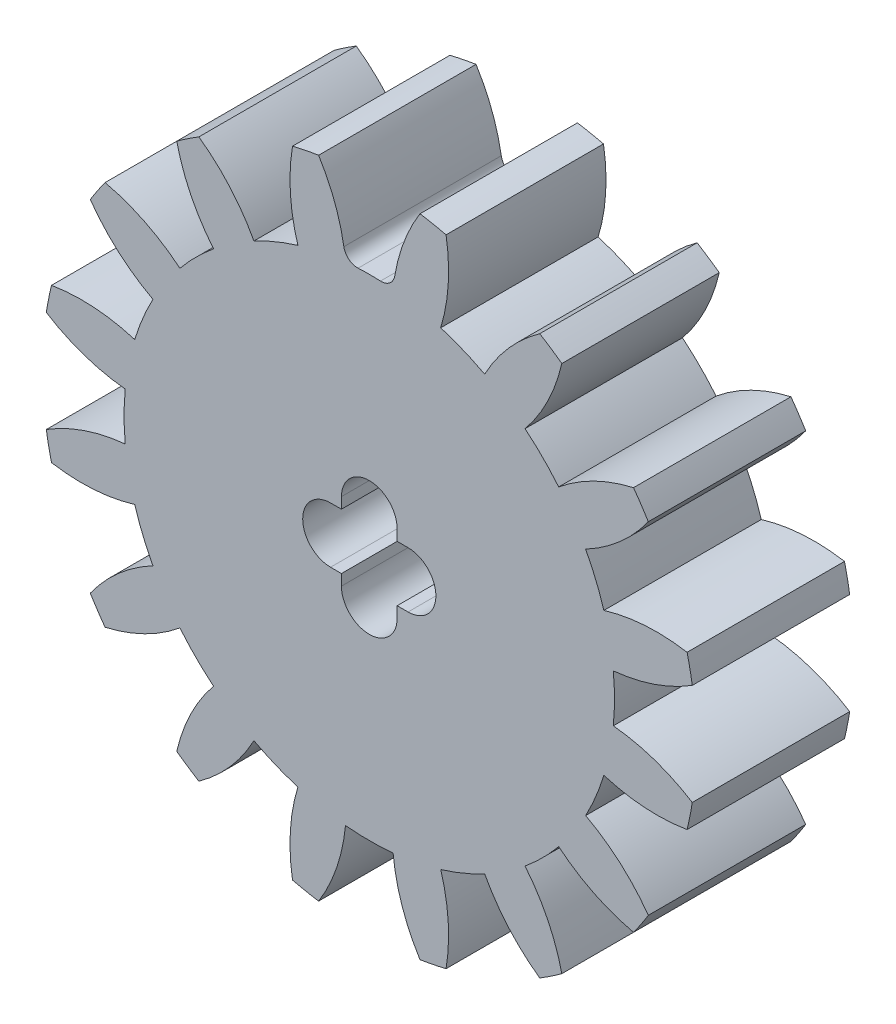
SolidWorks part; units mm, degrees
ref_plane "Front Plane" through (0, 0, 0) normal (0, 0, 1) x (1, 0, 0)
ref_plane "Top Plane" through (0, 0, 0) normal (0, 1, 0) x (1, 0, 0)
ref_plane "Right Plane" through (0, 0, 0) normal (1, 0, 0) x (0, 0, -1)
sketch "Sketch1" plane through (0, 0, 0) normal (0, 0, 1) x (1, 0, 0)
  line L0 (0, -1.6) -> (0, 1.6) construction
  line L1 (-1.15, -1.6) -> (-1.15, 1.6)
  line L2 (1.15, -1.6) -> (1.15, 1.6)
  line L3 (-1.6, 0) -> (1.6, 0) construction
  line L4 (-1.6, 1.15) -> (1.6, 1.15)
  line L5 (-1.6, -1.15) -> (1.6, -1.15)
  circle A0 centre (0, 0) radius 13.5
  arc A2 (-1.15, -1.6) -> (1.15, -1.6) centre (0, -1.6) ccw
  arc A3 (1.15, 1.6) -> (-1.15, 1.6) centre (0, 1.6) ccw
  arc A4 (-1.6, 1.15) -> (-1.6, -1.15) centre (-1.6, 0) ccw
  arc A5 (1.6, -1.15) -> (1.6, 1.15) centre (1.6, 0) ccw
  point P5 (0, 0)
  point P11 (0, 0)
  dimension "D2" = 27
  dimension "D1" = 5.5
  dimension "D3" = 5.5
  dimension "D4" = 2.3
  dimension "D5" = 2.3
extrude "Boss-Extrude1" add sketch "Sketch1" along normal mid plane 6.5 contours A0 A5 L5 L2 A2 L1 A4 L4 A3 region at (-13.1182, 0, 0)
sketch "Sketch2" plane through (0, 0, 0) normal (0, 0, 1) x (1, 0, 0)
  line L0 (0, 0) -> (0, 13.5) construction
  line L1 (0, 0) -> (-0.9822, 10.0772) construction
  line L2 (0, 8.0719) -> (-4.2467, 19.7397) construction
  arc A0 (1.3999, 11.9181) -> (-1.3999, 11.9181) centre (0, 0) ccw construction
  arc A1 (0.9822, 10.0772) -> (-0.9822, 10.0772) centre (0, 0) ccw
  arc A3 (2.0928, 13.3368) -> (-2.0928, 13.3368) centre (0, 0) ccw
  arc A4 (-0.9822, 10.0772) -> (-2.0928, 13.3368) centre (-8.4601, 9.3484) ccw
  arc A5 (0.9822, 10.0772) -> (2.0928, 13.3368) centre (8.4601, 9.3484) cw
  circle A6 centre (0, 0) radius 13.5 construction
  dimension "D1" = 24
  dimension "D2" = 3.375
  dimension "D3" = 20
  dimension "D4" = 2.8062
extrude "Cut-Extrude1" cut sketch "Sketch2" against normal through all both and the other way through all
fillet "Fillet1" radius 0.57 2 edges at (0.9822, 10.0772, 0) (-0.9822, 10.0772, 0)
pattern_circular "CirPattern3" count 16 over 360 about axis through (0, 0, 3.25) along (0, 0, -1) of "Cut-Extrude1"
equation "\"Module\"= 1.5"
equation "\"Pressure Angle\"= 20"
equation "\"Bore\"= 2"
equation "\"NumTeeth\"= 16"
equation "\"D2@Sketch1\"=(\"NumTeeth\"+2)*\"Module\""
equation "\"D1@Sketch2\"=\"NumTeeth\"*\"Module\""
equation "\"ToothDepth\"= IIF ( \"Module\" < 1.25 , 2.4 * \"Module\" , 2.25 * \"Module\" )"
equation "\"D2@Sketch2\"=\"ToothDepth\""
equation "\"D3@Sketch2\"=\"Pressure Angle\""
equation "\"D4@Sketch2\"=((\"Module\"*PI)/2)+0.3*\"Module\""
equation "\"D1@Fillet1\"=\"Module\"*0.38"
equation "\"D1@CirPattern3\"=\"NumTeeth\""
equation "\"D3@Sketch1\"=\"D1@Sketch1\""
equation "\"D5@Sketch1\"=\"D4@Sketch1\""
